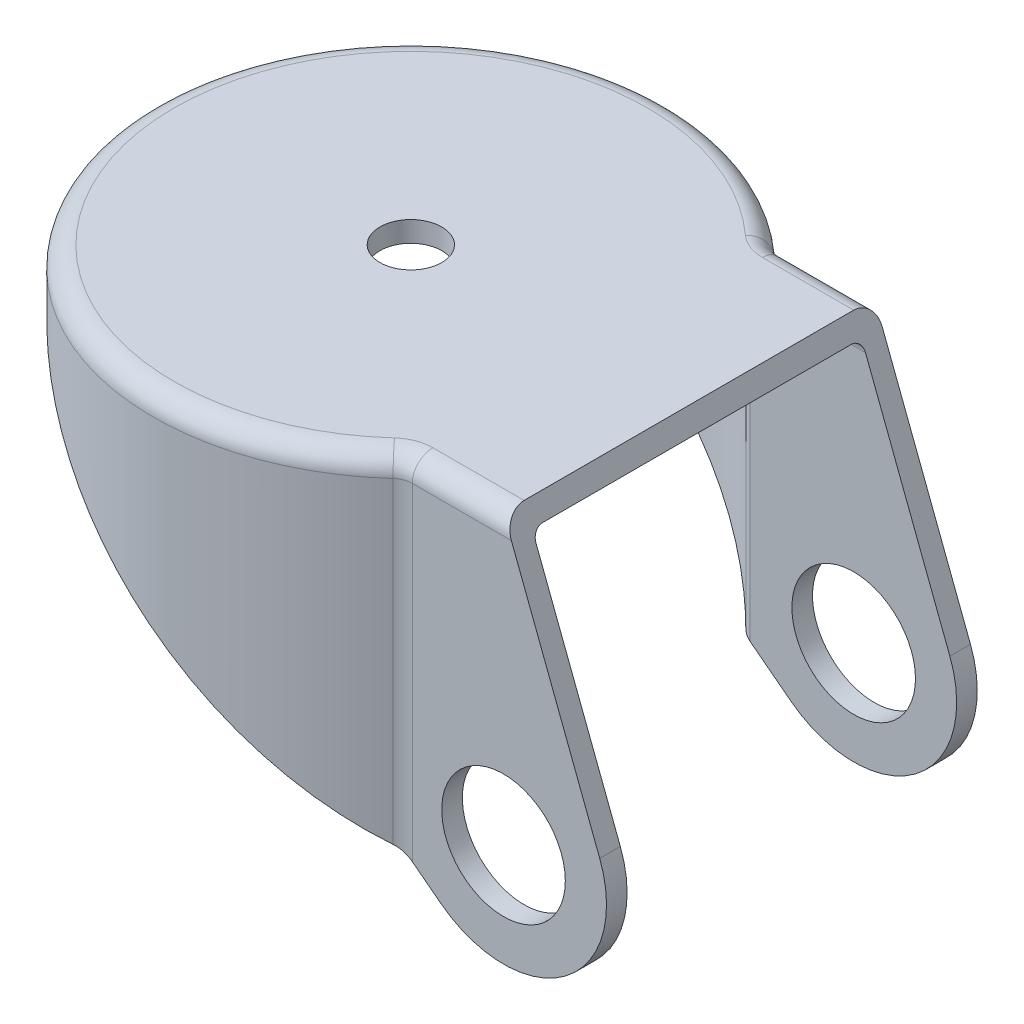
SolidWorks part; units mm, degrees
material "AISI 316 Tôle d'acier inoxydable (SS)"
ref_plane "Plan de face" through (0, 0, 0) normal (0, 0, 1) x (1, 0, 0)
ref_plane "Plan de dessus" through (0, 0, 0) normal (0, 1, 0) x (1, 0, 0)
ref_plane "Plan de droite" through (0, 0, 0) normal (1, 0, 0) x (0, 0, -1)
sketch "Esquisse1" plane through (0, 0, 0) normal (1, 0, 0) x (0, 0, -1)
  line L0 (0, 24.6119) -> (0, -17.4521) construction
  line L1 (-9, -5) -> (-9, 14)
  line L2 (-9, 14) -> (9, 14)
  line L3 (9, 14) -> (9, -5)
  line L4 (-22.5023, 0) -> (20.2009, 0) construction
  dimension "D1" = 14
  dimension "D2" = 18
  dimension "D3" = 5
  dimension "D4" = 5
extrude "Extru.-Mince1" add sketch "Esquisse1" along normal blind 5 and the other way blind 26 thin thin type one direction wall 1
sketch "Esquisse2" plane through (0, 0, 9) normal (0, 0, 1) x (1, 0, 0)
  line L0 (4.6702, 1.7857) -> (-1.8185, 18.7561)
  line L1 (5, -5) -> (5, 14) construction
  line L2 (0, -2.577) -> (0, 15.3368) construction
  line L3 (-3.0438, -3.9668) -> (-5, -2.4657)
  line L4 (-25.8355, 13) -> (-5, 13)
  line L5 (-26, 14) -> (5, 14) construction
  line L6 (-25.8355, 13) -> (-25.8355, -7.4538)
  line L7 (-25.8355, -7.4538) -> (8.2416, -7.4538)
  line L8 (8.2416, -7.4538) -> (8.2416, 18.7561)
  line L9 (8.2416, 18.7561) -> (-1.8185, 18.7561)
  line L10 (-26, -5) -> (5, -5) construction
  line L11 (-5, -2.4657) -> (-5, 13)
  circle A0 centre (0, 0) radius 3
  arc A1 (-3.0438, -3.9668) -> (4.6702, 1.7857) centre (0, 0) ccw
  point P4 (0, 14)
  dimension "D1" = 6
  dimension "D2" = 1
  dimension "D3" = 37.5
extrude "Enlèv. mat.-Extru.1" cut sketch "Esquisse2" against normal through all
sketch "Esquisse3" plane through (0, 14, 0) normal (0, 1, 0) x (1, 0, 0)
  line L0 (4.9042, 0) -> (-28.3941, 0) construction
  line L2 (-26, -9) -> (-26, 9) construction
  line L3 (-26, 9) -> (0, 9) construction
  line L4 (-4.8253, 9) -> (-4.8253, 9.9902)
  line L5 (-26, -9) -> (0, -9) construction
  line L6 (-4.8253, -9) -> (-3.7331, -11.3986)
  line L7 (-3.7331, -11.3986) -> (-26.0837, -19.5751)
  line L8 (-26.0837, -19.5751) -> (-28.8475, 16.2125)
  line L9 (-28.8475, 16.2125) -> (-6.7371, 16.2125)
  line L10 (-6.7371, 16.2125) -> (-4.8253, 9.9902)
  arc A0 (-4.8253, 9) -> (-4.8253, -9) centre (-13.5, 0) ccw
  point P7 (-4.8253, 9)
  point P8 (-4.8253, -9)
  dimension "D1" = 25
extrude "Enlèv. mat.-Extru.2" cut sketch "Esquisse3" against normal through all
sketch "Esquisse4" plane through (0, 14, 0) normal (0, 1, 0) x (1, 0, 0)
  line L0 (6.8163, 0) -> (-29.4631, 0) construction
  line L1 (-4.8253, 9) -> (-4.8253, -9)
  line L2 (-22.1747, 9) -> (0, 9) construction
  arc A0 (-4.8253, 9) -> (-4.8253, -9) centre (-13.5, 0) ccw
  dimension "D1" = 25
extrude "Boss.-Extru.1" add sketch "Esquisse4" against normal blind 1
sketch "Esquisse5" plane through (0, 13, 0) normal (0, -1, 0) x (1, 0, 0)
  line L0 (-4.8253, 9) -> (-4.8253, 7.5498)
  line L1 (-4.8253, -9) -> (-4.8253, -7.5498)
  arc A0 (-4.8253, 9) -> (-4.8253, -9) centre (-13.5, 0) ccw
  arc A1 (-4.8253, 9) -> (-4.8253, -9) centre (-13.5, 0) ccw construction
  arc A2 (-4.8253, 7.5498) -> (-4.8253, -7.5498) centre (-13.5, 0) ccw
  dimension "D1" = 23
extrude "Boss.-Extru.2" add sketch "Esquisse5" along normal blind 20
sketch "Esquisse6" plane through (0, 0, 0) normal (0, 0, 1) x (1, 0, 0)
  line L0 (0.0582, -6.347) -> (-23.8521, 12)
  line L1 (-23.8521, 12) -> (-28.1771, 12)
  line L2 (-4.8253, 14) -> (-26, 14) construction
  line L3 (-28.1771, 12) -> (-28.1771, -8.3903)
  line L4 (-28.1771, -8.3903) -> (0.4398, -8.9907)
  line L5 (0.4398, -8.9907) -> (0.0582, -6.347)
  arc A0 (-3.0438, -3.9668) -> (4.6702, 1.7857) centre (0, 0) ccw construction
  dimension "D1" = 2
  dimension "D2" = 37.5
extrude "Enlèv. mat.-Extru.3" cut sketch "Esquisse6" along normal through all and the other way through all
sketch "Esquisse7" plane through (0, 13, 0) normal (0, -1, 0) x (1, 0, 0)
  line L0 (-4.8253, -8) -> (0.3824, -8) construction
  line L1 (-3.0438, 8) -> (-8.5159, 8)
  line L2 (-3.0438, 8) -> (-3.0438, -8)
  line L3 (-3.0438, -8) -> (-8.5159, -8)
  line L4 (-8.5159, 8) -> (-8.5159, -8)
extrude "Enlèv. mat.-Extru.4" cut sketch "Esquisse7" along normal blind 20
sketch "Esquisse8" plane through (0, 14, 0) normal (0, 1, 0) x (1, 0, 0)
  circle A0 centre (-13.5, 0) radius 1.5
  arc A1 (-4.8253, 9) -> (-4.8253, -9) centre (-13.5, 0) ccw construction
  dimension "D1" = 3
extrude "Enlèv. mat.-Extru.5" cut sketch "Esquisse8" against normal through all
fillet "Congé1" radius 1 5 edges at (-2.4127, 14, 9) (-2.4127, 14, -9) (-26, 14, 0) (-4.8253, 5.7001, -9) (-4.8253, 5.7001, 9)
fillet "Congé2" radius 0.5 5 edges at (-5.2386, 5.3587, -8) (-5.2386, 5.3587, 8) (-2.4281, 13, 8) (-2.4281, 13, -8) (-25, 13, 0)
